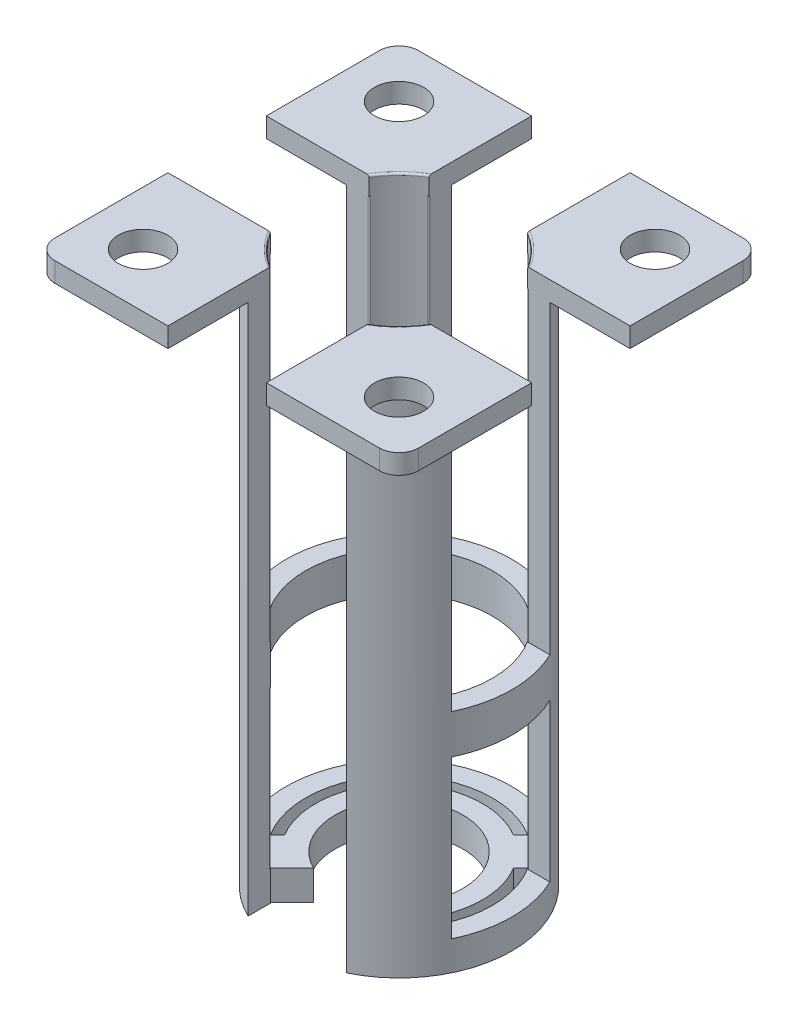
SolidWorks part; units mm, degrees
note: The reader was unsure of these and kept them because the rebuilt part matched: shared geometry of "Sketch5<5>".
ref_plane "Front Plane" through (0, 0, 0) normal (0, 0, 1) x (1, 0, 0)
ref_plane "Top Plane" through (0, 0, 0) normal (0, 1, 0) x (1, 0, 0)
ref_plane "Right Plane" through (0, 0, 0) normal (1, 0, 0) x (0, 0, -1)
sketch "Sketch5" plane through (0, 0, 0) normal (0, 1, 0) x (1, 0, 0)
  line L1 (-23.475, -23.475) -> (23.475, -23.475)
  line L2 (-23.475, -23.475) -> (-23.475, 23.475)
  line L3 (-23.475, 23.475) -> (23.475, 23.475)
  line L4 (23.475, -23.475) -> (23.475, 23.475)
  line L5 (-23.475, -23.475) -> (23.475, 23.475) construction
  line L6 (-23.475, 23.475) -> (23.475, -23.475) construction
  circle A0 centre (0, 0) radius 12.045
  circle A1 centre (0, 0) radius 14.585
  dimension "D1" = 24.09
  dimension "D3" = 29.17
  dimension "D2" = 46.95
extrude "Boss-Extrude2" add sketch "Sketch5" against normal blind 71.15 separate body contours L1 L4 L3 L2 A1 | A1 A0
extrude "Cut-Extrude2" cut sketch "Sketch5<5>" against normal up to next from offset 2.54 contours L1 L4 L3 L2 A1 offset against normal yes
sketch "Sketch5<5>" plane through (0, 0, 0) normal (0, 1, 0) x (1, 0, 0) same geometry as "Sketch5"
sketch "Sketch10" plane through (23.475, 0, 0) normal (1, 0, 0) x (0, 0, -1)
  line L0 (-23.475, -2.54) -> (23.475, -2.54) construction
  line L1 (-14.585, -71.15) -> (14.585, -71.15) construction
  line L2 (-6.35, -2.54) -> (6.35, -2.54)
  line L3 (-6.35, -2.54) -> (-6.35, -71.15)
  line L4 (-6.35, -71.15) -> (6.35, -71.15)
  line L5 (6.35, -2.54) -> (6.35, -71.15)
  point P8 (0, -2.54)
  dimension "D1" = 12.7
extrude "Cut-Extrude3" cut sketch "Sketch10" against normal through all
pattern_circular "CirPattern2" count 2 every 90 of "Cut-Extrude3"
sketch "Sketch12" plane through (0, 0, 23.475) normal (0, 0, 1) x (1, 0, 0)
  line L0 (-23.475, 0) -> (23.475, 0) construction
  line L1 (-6.35, 0) -> (6.35, 0)
  line L2 (-6.35, 0) -> (-6.35, -2.54)
  line L3 (-6.35, -2.54) -> (6.35, -2.54)
  line L4 (6.35, 0) -> (6.35, -2.54)
  line L6 (-23.475, -2.54) -> (23.475, -2.54) construction
  point P6 (0, 0)
  dimension "D1" = 12.7
extrude "Cut-Extrude4" cut sketch "Sketch12" against normal up to next
fillet "Fillet6" radius 0.254 16 edges at (8.5171, -71.15, -8.5171) (-8.5171, -71.15, 8.5171) (-12.045, -2.54, 0) (12.045, -2.54, 0) (-10.2352, -36.845, -6.35) (10.2352, -36.845, -6.35) (10.2352, -36.845, 6.35) (-10.2352, -36.845, 6.35) (0, 0, -12.045) (-8.5171, -71.15, -8.5171) (8.5171, -71.15, 8.5171) (0, -2.54, -12.045) (-6.35, -35.575, 10.2352) (-6.35, -36.845, -10.2352) (6.35, -36.845, -10.2352) (6.35, -35.575, 10.2352)
fillet "Fillet10" radius 2.54 4 edges at (-23.475, -1.27, 23.475) (-23.475, -1.27, -23.475) (23.475, -1.27, -23.475) (23.475, -1.27, 23.475)
sketch "Sketch13" plane through (0, -2.54, 0) normal (0, -1, 0) x (1, 0, 0)
  line L0 (-22.7311, 22.7311) -> (-10.3132, 10.3132) construction
  line L5 (0, -25.8225) -> (0, 25.8225) construction
  line L6 (25.8225, 0) -> (-25.8225, 0) construction
  circle A0 centre (-16.5221, 16.5221) radius 3.175
  circle A1 centre (16.5221, 16.5221) radius 3.175
  circle A2 centre (16.5221, -16.5221) radius 3.175
  circle A3 centre (-16.5221, -16.5221) radius 3.175
  arc A4 (-20.935, 23.475) -> (-23.475, 20.935) centre (-20.935, 20.935) ccw construction
  arc A5 (-6.35, 13.1301) -> (-13.1301, 6.35) centre (0, 0) ccw construction
  point P2 (-16.5221, 16.5221)
  dimension "D1" = 6.35
extrude "Cut-Extrude5" cut sketch "Sketch13" against normal up to next
ref_plane "Plane1" through (0, -67.34, 0) normal (0, -1, 0) x (-1, 0, 0)
sketch "Sketch23" plane through (0, -67.34, 0) normal (0, -1, 0) x (-1, 0, 0)
  line L0 (-18.395, -18.395) -> (18.395, -18.395)
  line L1 (-18.395, -18.395) -> (-18.395, 18.395)
  line L2 (-18.395, 18.395) -> (18.395, 18.395)
  line L3 (18.395, -18.395) -> (18.395, 18.395)
  line L4 (-18.395, -18.395) -> (18.395, 18.395) construction
  line L5 (-18.395, 18.395) -> (18.395, -18.395) construction
  circle A0 centre (0, 0) radius 12.045
  circle A1 centre (0, 0) radius 14.585
  dimension "D1" = 24.09
  dimension "D2" = 29.17
  dimension "D3" = 18.395
extrude "Boss-Extrude3" add sketch "Sketch23" along normal up to surface (3.81 mm away) contours A1 A0 up to face at (9.2978, -71.15, 9.2978)
sketch "Sketch26" plane through (0, -67.34, 0) normal (0, -1, 0) x (-1, 0, 0)
  line L0 (-6.4676, 10.1613) -> (10.1613, -6.4676)
  line L1 (-10.1613, 6.4676) -> (6.4676, -10.1613)
  line L2 (6.4676, 10.1613) -> (-10.1613, -6.4676)
  line L3 (10.1613, 6.4676) -> (-6.4676, -10.1613)
  circle A0 centre (0, 0) radius 4.5 construction
  circle A1 centre (0, 0) radius 8.235
  circle A2 centre (0, 0) radius 10.775
  circle A3 centre (0, 0) radius 12.045
  dimension "D1" = 9
  dimension "D2" = 16.47
  dimension "D3" = 21.55
  dimension "D4" = 24.09
extrude "Boss-Extrude4" add sketch "Sketch26" along direction (0, 1, 0) on the side of the normal up to surface (3.81 mm away) contours L0 A3 L1 A2 | L3 A3 L2 A2 | L1 A3 L0 A2 | L2 A3 L3 A2 | L1 A2 L0 A1 | L2 A2 L3 A1 | L1 A2 L2 A1 | L0 A2 L1 A1 | L2 A2 L0 A1 | L3 A2 L2 A1 | L0 A2 L3 A1
sketch "Sketch31" plane through (0, -67.34, 0) normal (0, 1, 0) x (1, 0, 0)
  line L0 (-6.35, -13.1301) -> (-6.35, -10.2352)
  line L3 (6.35, -13.1301) -> (6.35, -10.2352)
  line L4 (-6.35, -10.3756) -> (-6.35, -13.1301) construction
  arc A1 (-6.4676, -10.1613) -> (6.4676, -10.1613) centre (0, 0) ccw
  arc A2 (-6.35, -13.1301) -> (6.35, -13.1301) centre (0, 0) ccw
  line M3 (-6.35, -10.3756) -> (-6.35, -13.1301)
  arc M4 (-6.35, -13.1301) -> (6.35, -13.1301) centre (0, 0) ccw
  line M5 (6.35, -13.1301) -> (6.35, -10.3756)
  arc M7 (6.4676, -10.1613) -> (-6.4676, -10.1613) centre (0, 0) cw
  dimension "D1" = 12.045
extrude "Cut-Extrude7" cut sketch "Sketch31" against normal through all contours L3 L0 M5 M7 M3 M4
ref_plane "Plane2" through (0, -41.94, 0) normal (0, -1, 0) x (-1, 0, 0)
sketch "Sketch32" plane through (0, -41.94, 0) normal (0, -1, 0) x (-1, 0, 0)
  line L0 (-6.35, -13.1301) -> (-6.35, -10.2352)
  line L1 (6.35, -10.2352) -> (6.35, -13.1301)
  arc A0 (6.35, -13.1301) -> (-6.35, -13.1301) centre (0, 0) ccw
  arc A1 (6.35, -10.2352) -> (-6.35, -10.2352) centre (0, 0) ccw
extrude "Boss-Extrude6" add sketch "Sketch32" along normal blind 5.08
pattern_circular "CirPattern6" count 4 every 90 about axis through (0, 0, 0) along (0, 1, 0) of "Cut-Extrude4"
equation "\"diameter\"= 21.55mm"
equation "\"height\"= 68.15mm"
equation "\"D1@Sketch5\"=\"diameter\"+.1"
equation "\"D2@Sketch5\"=\"diameter\"+1"
equation "\"D1@Boss-Extrude2\"=\"height\" + 3mm"
equation "\"D3@Sketch5\"=\"diameter\"+.3"
equation "\"slitwidth\"= 0.5"
equation "\"D1@Sketch10\"=\"slitwidth\""
equation "\"D1@Sketch12\"=\"slitwidth\""
equation "\"screw\"= .25"
equation "\"nipple\"=0.354331"
equation "\"D1@Sketch26\"=\"nipple\""
equation "\"D2@Sketch26\"=\"diameter\"-.2in"
equation "\"D3@Sketch26\"=\"diameter\""
equation "\"D4@Sketch26\"=\"diameter\"+.1"
equation "\"bolt\"= 0.25"
equation "\"D1@Sketch13\"=\"bolt\""
equation "\"radius\"= 2.61888"
